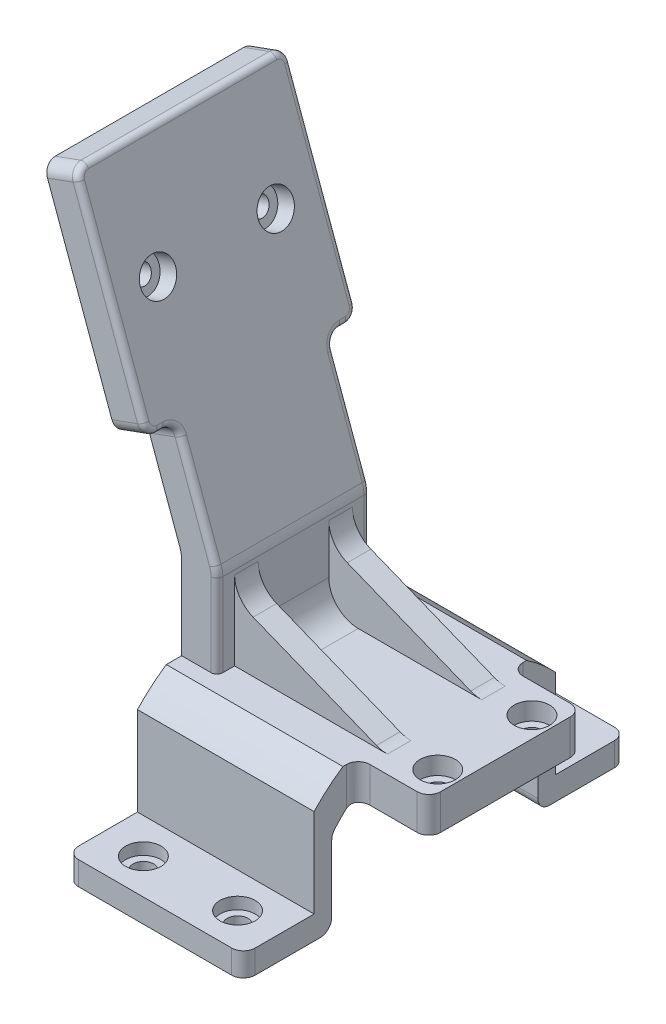
SolidWorks part; units mm, degrees
ref_plane "前视基准面" through (0, 0, 0) normal (0, 0, 1) x (1, 0, 0)
ref_plane "上视基准面" through (0, 0, 0) normal (0, 1, 0) x (1, 0, 0)
ref_plane "右视基准面" through (0, 0, 0) normal (1, 0, 0) x (0, 0, -1)
other "Configuration Table"
sketch "草图1" plane through (0, 0, 0) normal (0, 1, 0) x (1, 0, 0)
  line L0 (-21, 0) -> (21, 0) construction
  line L1 (-21, 13) -> (21, 13)
  line L2 (-21, 13) -> (-21, -13)
  line L3 (-21, -13) -> (21, -13)
  line L4 (21, 13) -> (21, -13)
  line L5 (-21, 13) -> (21, -13) construction
  line L6 (-21, -13) -> (21, 13) construction
  circle A0 centre (17.5, 8) radius 1.7
  circle A1 centre (17.5, -8) radius 1.7
  point P0 (0, 0)
  dimension "D3" = 8
  dimension "D4" = 3.4
  dimension "D5" = 3.5
  dimension "D1" = 42
  dimension "D2" = 26
extrude "凸台-拉伸1" add sketch "草图1" along normal blind 6
sketch "草图15" plane through (0, 6, 0) normal (0, 1, 0) x (1, 0, 0)
  line L0 (-21, -13) -> (21, -13) construction
  line L1 (-21, 13) -> (-15, 13)
  line L2 (-21, 13) -> (-21, -13)
  line L3 (-21, -13) -> (-15, -13)
  line L4 (-15, 13) -> (-15, -13)
  dimension "D1" = 6
extrude "凸台-拉伸4" add sketch "草图15" along normal blind 15
sketch "草图16" plane through (0, 0, 13) normal (0, 0, 1) x (1, 0, 0)
  line L0 (-15, 21) -> (-21.8582, 39.8428)
  line L1 (-21.8582, 39.8428) -> (-27.1564, 37.9145)
  line L2 (-27.1564, 37.9145) -> (-21, 21)
  line L3 (-15, 21) -> (-15, 6) construction
  line L4 (-21, 21) -> (-15, 21) construction
  line L5 (-21, 21) -> (-15, 21)
  dimension "D1" = 20
  dimension "D2" = 18
extrude "凸台-拉伸5" add sketch "草图16" against normal up to surface (26 mm away) up to face at (-5, 9, -13)
sketch "草图17" plane through (-11.7942, -4.2927, 0) normal (-0.9397, -0.342, 0) x (0, 0, 1)
  line L0 (0, 44.916) -> (0, 62.916) construction
  line L1 (-13, 44.916) -> (13, 44.916) construction
  line L2 (-18, 62.916) -> (18, 62.916) construction
  line L3 (-18, 80.916) -> (18, 80.916)
  line L4 (-18, 80.916) -> (-18, 44.916)
  line L5 (-18, 44.916) -> (18, 44.916)
  line L6 (18, 80.916) -> (18, 44.916)
  line L7 (-18, 80.916) -> (18, 44.916) construction
  line L8 (-18, 44.916) -> (18, 80.916) construction
  circle A0 centre (10, 62.916) radius 1.6
  circle A1 centre (-10, 62.916) radius 1.6
  dimension "D3" = 3.2
  dimension "D4" = 10
  dimension "D1" = 36
  dimension "D2" = 36
extrude "凸台-拉伸6" add sketch "草图17" against normal up to surface (5.6382 mm away) up to face at (-18.4291, 30.4214, 0)
fillet "圆角3" radius 2 6 edges at (-24.5073, 38.8786, -13) (-24.5073, 38.8786, 13) (-36.82, 72.7076, 18) (-24.5073, 38.8786, 18) (-24.5073, 38.8786, -18) (-36.82, 72.7076, -18)
sketch "草图18" plane through (-6.4961, -2.3644, 0) normal (0.9397, 0.342, 0) x (0, 0, -1)
  circle A0 centre (-10, 62.916) radius 3
  circle A1 centre (10, 62.916) radius 3
  dimension "D1" = 6
  dimension "D2" = 6
extrude "切除-拉伸4" cut sketch "草图18" against normal blind 3
sketch "草图19" plane through (0, 6, 0) normal (0, 1, 0) x (1, 0, 0)
  circle A0 centre (17.5, 8) radius 3
  circle A1 centre (17.5, -8) radius 3
  dimension "D1" = 6
  dimension "D2" = 6
extrude "切除-拉伸5" cut sketch "草图19" against normal blind 3
fillet "圆角4" radius 1 15 edges at (-18.0871, 29.4817, 13) (-21.6579, 39.2924, 13.5858) (-21.8582, 39.8428, 15.5) (-22.0586, 40.3933, 17.4142) (-28.0146, 56.7573, 18) (-33.9706, 73.1213, 17.4142) (-18.0871, 29.4817, -13) (-21.6579, 39.2924, -13.5858) (-21.8582, 39.8428, -15.5) (-22.0586, 40.3933, -17.4142) (-28.0146, 56.7573, -18) (-33.9706, 73.1213, -17.4142) (-15, 13.5, -13) (-15, 13.5, 13) (-34.171, 73.6718, 0)
fillet "圆角6" radius 5 4 edges at (-15.2929, 20.9484, -12.7071) (-15.2929, 20.9484, 12.7071) (-15, 21, 0) (-21, 21, 0)
ref_plane "基准面2" through (0, 0, 8) normal (0, 0, 1) x (1, 0, 0)
sketch "草图20" plane through (0, 0, 8) normal (0, 0, 1) x (1, 0, 0)
  line L0 (-15, 16) -> (10, 6)
  line L1 (-15, 20.1184) -> (-15, 6) construction
  line L3 (10, 6) -> (-15, 6)
  line L4 (-15, 6) -> (-15, 16)
  dimension "D1" = 10
  dimension "D2" = 25
extrude "凸台-拉伸7" add sketch "草图20" along normal mid plane 4
ref_plane "基准面3" through (0, 0, 0) normal (0, 0, -1) x (-1, 0, 0)
mirror "镜向1" about plane through (0, 0, 0) normal (0, 0, -1) of "凸台-拉伸7"
fillet "圆角7" radius 5 4 edges at (-15, 16, -8) (10, 6, -8) (10, 6, 8) (-15, 16, 8)
fillet "圆角8" radius 5 1 edges at (-15, 6, 0)
sketch "草图21" plane through (0, 6, 0) normal (0, 1, 0) x (1, 0, 0)
  line L0 (-15, 0) -> (21, 0) construction
  line L1 (-15, -6) -> (-15, 6) construction
  line L2 (21, -13) -> (21, 13) construction
  line L3 (-16, -13) -> (21, -13) construction
  line L4 (9, -13) -> (-21, -13)
  line L5 (9, -13) -> (9, -20.5)
  line L6 (9, -20.5) -> (-21, -20.5)
  line L7 (-21, -13) -> (-21, -20.5)
  line L8 (21, -13) -> (21, 13) construction
  dimension "D1" = 12
  dimension "D2" = 30
  dimension "D3" = 20.5
extrude "凸台-拉伸8" add sketch "草图21" against normal up to surface (6 mm away) up to face at (0, 0, 0)
sketch "草图23" plane through (0, 0, 0) normal (0, -1, 0) x (1, 0, 0)
  line L0 (-21, 20.5) -> (-21, -13) construction
  line L1 (9, 20.5) -> (-21, 20.5)
  line L2 (9, 20.5) -> (9, 17.5)
  line L3 (9, 17.5) -> (-21, 17.5)
  line L4 (-21, 20.5) -> (-21, 17.5)
  dimension "D1" = 3
extrude "凸台-拉伸9" add sketch "草图23" along normal blind 17.25
sketch "草图24" plane through (0, 0, 20.5) normal (0, 0, 1) x (1, 0, 0)
  line L0 (9, -17.25) -> (9, 6) construction
  line L1 (-21, -17.25) -> (9, -17.25)
  line L2 (-21, -17.25) -> (-21, -13.25)
  line L3 (-21, -13.25) -> (9, -13.25)
  line L4 (9, -17.25) -> (9, -13.25)
  dimension "D1" = 4
extrude "凸台-拉伸10" add sketch "草图24" along normal blind 12
sketch "草图26" plane through (-21, 0, 0) normal (-1, 0, 0) x (0, 0, 1)
  line L0 (17.5, -17.25) -> (17.5, 0) construction
  line L1 (17.5, 0) -> (-13, 0) construction
  line L2 (17.5, -3.1079) -> (17.5, 0)
  line L3 (17.5, 0) -> (14.446, 0)
  arc A0 (17.5, -3.1079) -> (14.446, 0) centre (0, -17.25) ccw
  dimension "D2" = 45
  dimension "D1" = 17.25
extrude "凸台-拉伸11" add sketch "草图26" against normal up to surface (30 mm away) up to face at (9, -6.125, 20.875)
fillet "圆角9" radius 2 2 edges at (-6, 0, 14.446) (-6, -3.1079, 17.5)
sketch "草图28" plane through (-21, 0, 0) normal (-1, 0, 0) x (0, 0, 1)
  line L0 (20.5, -13.25) -> (20.5, 6) construction
  line L1 (13, 6) -> (20.5, 6) construction
  line L2 (20.5, 1.8222) -> (20.5, 6)
  line L3 (15.6025, 6) -> (20.5, 6)
  arc A0 (20.5, 1.8222) -> (15.6025, 6) centre (0, -17.25) ccw
  arc A1 (17.0122, -2.5247) -> (15.0365, -0.5122) centre (0, -17.25) ccw construction
  dimension "D1" = 56
extrude "切除-拉伸6" cut sketch "草图28" against normal blind 38
fillet "圆角11" radius 2 3 edges at (-6, -17.25, 17.5) (-21, -15.25, 32.5) (9, -15.25, 32.5)
sketch "草图29" plane through (0, -13.25, 0) normal (0, 1, 0) x (1, 0, 0)
  line L0 (-6, -32.5) -> (-6, -20.5) construction
  line L1 (7, -32.5) -> (-19, -32.5) construction
  line L2 (9, -20.5) -> (-21, -20.5) construction
  line L3 (-21, -26.5) -> (9, -26.5) construction
  line L4 (-21, -30.5) -> (-21, -20.5) construction
  line L5 (9, -30.5) -> (9, -20.5) construction
  circle A0 centre (2, -26.5) radius 1.75
  circle A1 centre (-14, -26.5) radius 1.75
  dimension "D2" = 8
  dimension "D3" = 3.5
  dimension "D1" = 6
extrude "切除-拉伸7" cut sketch "草图29" against normal blind 38
sketch "草图30" plane through (0, -13.25, 0) normal (0, 1, 0) x (1, 0, 0)
  circle A0 centre (2, -26.5) radius 3
  circle A1 centre (-14, -26.5) radius 3
  dimension "D1" = 6
  dimension "D2" = 6
extrude "切除-拉伸8" cut sketch "草图30" against normal blind 2
ref_plane "基准面4" through (0, 0, 0) normal (0, 0, 1) x (1, 0, 0)
mirror "镜向2" about plane through (0, 0, 0) normal (0, 0, 1) of "切除-拉伸8", "切除-拉伸7", "圆角11", "切除-拉伸6", "圆角9", "凸台-拉伸11", "凸台-拉伸10", "凸台-拉伸9", "凸台-拉伸8"
fillet "圆角14" radius 2 4 edges at (9, 3, -13) (9, 3, 13) (21, 3, -13) (21, 3, 13)
